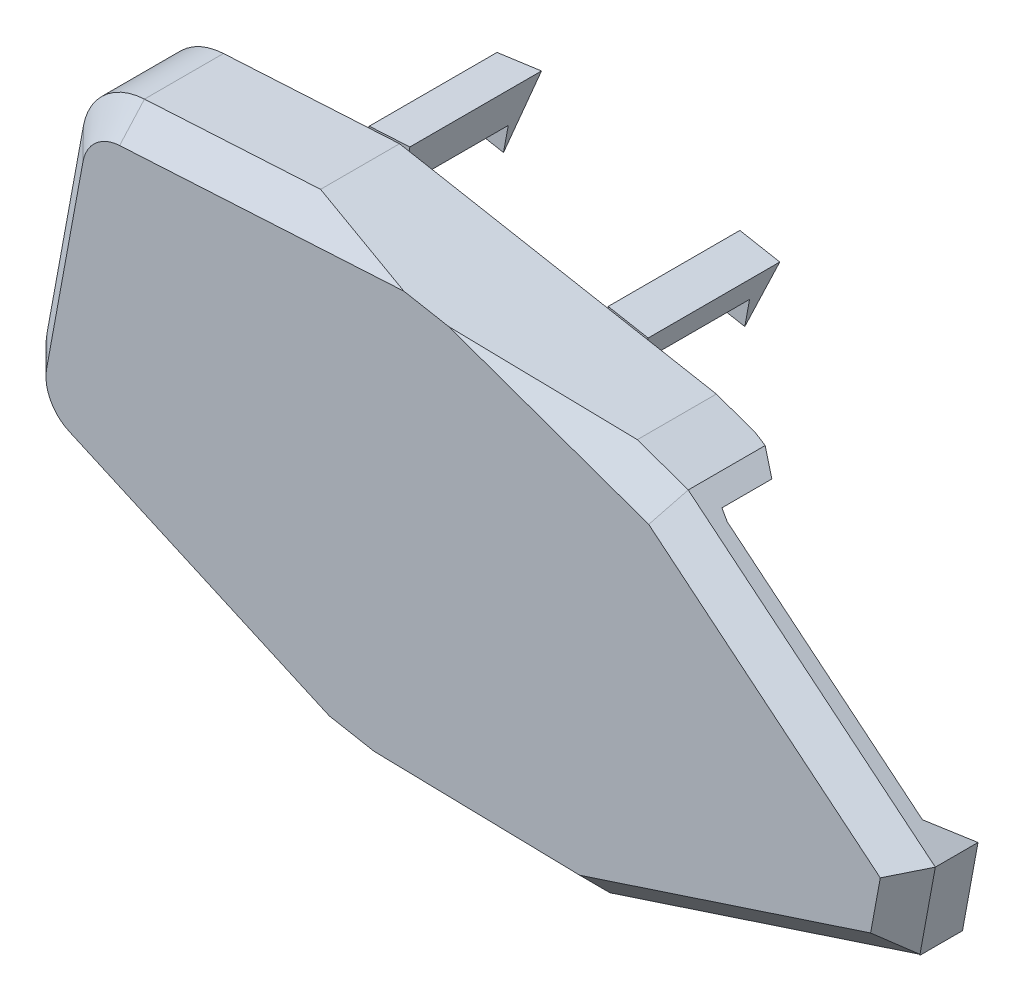
SolidWorks part; units mm, degrees
ref_plane "Front Plane" through (0, 0, 0) normal (0, 0, 1) x (1, 0, 0)
ref_plane "Top Plane" through (0, 0, 0) normal (0, 1, 0) x (1, 0, 0)
ref_plane "Right Plane" through (0, 0, 0) normal (1, 0, 0) x (0, 0, -1)
sketch "Sketch1" plane through (0, 0, 0) normal (0, 0, 1) x (1, 0, 0)
  line L0 (-54.3202, -28.2496) -> (-51.5581, -13.2557)
  line L2 (-46.9215, -9.1694) -> (-33.5467, -8.4176)
  line L3 (-33.5467, -8.4176) -> (-9.4849, -12.8501)
  line L5 (-9.4849, -12.8501) -> (10.6469, -20.0271)
  line L6 (13.8852, -25.6426) -> (11.2412, -39.9955)
  line L7 (-52.9392, -20.7527) -> (12.5632, -32.8191) construction
  line L8 (-15.1533, -43.6208) -> (6.2145, -44.0885)
  line L9 (-39.2151, -39.1883) -> (-15.1533, -43.6208)
  line L10 (-51.444, -33.7198) -> (-39.2151, -39.1883)
  arc A0 (6.2145, -44.0885) -> (11.2412, -39.9955) centre (6.3239, -39.0897) ccw
  arc A1 (10.6469, -20.0271) -> (13.8852, -25.6426) centre (8.9679, -24.7368) cw
  arc A2 (-51.444, -33.7198) -> (-54.3202, -28.2496) centre (-49.4029, -29.1554) cw
  arc A3 (-51.5581, -13.2557) -> (-46.9215, -9.1694) centre (-46.6409, -14.1616) cw
  point P16 (10.47, -44.1817)
  point P19 (14.6563, -21.4565)
  point P22 (-55.0323, -32.1153)
  point P25 (-50.846, -9.3901)
  dimension "D1" = 5
extrude "Boss-Extrude1" add sketch "Sketch1" along normal blind 8
sketch "Sketch2" plane through (0, 0, 0) normal (0, 0, -1) x (-1, 0, 0)
  line L0 (53.0576, -29.6753) -> (49.8455, -12.2387)
  line L1 (7.688, -29.0189) -> (66.6951, -18.149) construction
  line L2 (47.8786, -10.6011) -> (29.9733, -10.6011)
  line L3 (29.9733, -10.6011) -> (5.1379, -15.1761)
  line L4 (1.3472, 5.402) -> (14.0287, -63.4397) construction
  line L5 (9.4849, -12.8501) -> (33.5467, -8.4176) construction
  line L6 (33.5467, -8.4176) -> (46.9215, -9.1694) construction
  line L7 (51.5581, -13.2557) -> (54.3202, -28.2496) construction
  line L8 (5.1379, -15.1761) -> (-10.1011, -22.0315)
  line L9 (-8.9937, -21.8275) -> (-15.2261, -22.9756) construction
  line L10 (-10.1011, -22.0315) -> (-10.675, -22.2897)
  line L11 (51.4516, -20.957) -> (7.688, -29.0189) construction
  line L12 (51.8034, -31.9064) -> (35.0734, -38.2866)
  line L13 (35.0734, -38.2866) -> (10.238, -42.8617)
  line L14 (-6.4435, -41.8865) -> (-7.0718, -41.8498)
  line L15 (10.238, -42.8617) -> (-6.4435, -41.8865)
  line L16 (-8.922, -40.2155) -> (-11.8214, -24.4759)
  arc A1 (-7.0718, -41.8498) -> (-8.922, -40.2155) centre (-6.9551, -39.8532) cw
  arc A2 (51.8034, -31.9064) -> (53.0576, -29.6753) centre (51.0907, -30.0376) ccw
  arc A3 (49.8455, -12.2387) -> (47.8786, -10.6011) centre (47.8786, -12.6011) ccw
  arc A4 (-10.675, -22.2897) -> (-11.8214, -24.4759) centre (-9.8545, -24.1136) ccw
  point P26 (-8.6378, -41.7582)
  point P29 (53.3593, -31.313)
  point P32 (49.5439, -10.6011)
  point P35 (-12.1056, -22.9332)
  dimension "D4" = 2
  dimension "D1" = 1.5
  dimension "D2" = 2.3806
  dimension "D3" = 1.5
extrude "Cut-Extrude1" cut sketch "Sketch2" against normal blind 5
chamfer "Chamfer1" distance 2 angle 45 5 edges at (-4.4694, -43.8546, 8) (9.4809, -42.967, 8) (12.5632, -32.8191, 8) (13.2993, -22.239, 8) (0.581, -16.4386, 8)
chamfer "Chamfer2" distance 2 angle 45 5 edges at (-45.3295, -36.4541, 8) (-53.8285, -31.4823, 8) (-52.9392, -20.7527, 8) (-49.9468, -10.4104, 8) (-40.2341, -8.7935, 8)
sketch "Sketch3" plane through (0, 0, 0) normal (0, 0, -1) x (-1, 0, 0)
  line L0 (23.3947, -42.1026) -> (23.0981, -40.4927)
  line L1 (39.2151, -39.1883) -> (15.1533, -43.6208) construction
  line L2 (10.238, -42.8617) -> (35.0734, -38.2866) construction
  line L3 (38.0004, -36.6537) -> (38.5242, -39.4972)
  line L5 (23.3947, -42.1026) -> (20.3598, -42.6617)
  line L6 (20.3598, -42.6617) -> (20.0632, -41.0517)
  line L7 (20.0632, -41.0517) -> (23.0981, -40.4927)
  line L8 (51.444, -33.7198) -> (39.2151, -39.1883) construction
  line L9 (38.0004, -36.6537) -> (40.9507, -36.1102)
  line L10 (40.9507, -36.1102) -> (41.3425, -38.2369)
  line L11 (40.9507, -36.1102) -> (41.3131, -38.0771) construction
  line L12 (38.3627, -38.6206) -> (38.0004, -36.6537) construction
  line L13 (38.5242, -39.4972) -> (41.3425, -38.2369)
  line L14 (7.688, -29.0189) -> (20.0756, -26.7369) construction
  line L15 (7.688, -29.0189) -> (66.6951, -18.149) construction
  line L16 (33.2901, -11.0839) -> (32.7662, -8.2403)
  line L17 (33.2901, -11.0839) -> (36.2404, -10.5404)
  line L18 (36.2404, -10.5404) -> (35.8486, -8.4136)
  line L19 (32.7662, -8.2403) -> (35.8486, -8.4136)
  line L20 (14.9631, -13.3662) -> (17.9981, -12.8071)
  line L21 (14.6666, -11.7562) -> (14.9631, -13.3662)
  line L22 (17.7015, -11.1971) -> (14.6666, -11.7562)
  line L23 (17.7015, -11.1971) -> (17.9981, -12.8071)
extrude "Boss-Extrude2" add sketch "Sketch3" along normal blind 10
chamfer "Chamfer3" distance 5 angle 45 5 edges at (-1.5831, -42.3557, 0) (8.2791, -41.3521, 0) (10.3717, -32.3457, 0) (11.6258, -23.1848, 0) (2.7686, -18.7329, 0)
chamfer "Chamfer5" distance 1 angle 45 9 edges at (-29.0858, -39.3896, 0) (-40.786, -36.1405, 0) (-36.0757, -10.5707, 0) (-7.7976, -14.6861, 0) (-23.9857, -11.7041, 0) (-12.4809, -42.4485, 0) (-52.8341, -31.0177, 0) (-51.4516, -20.957, 0) (-49.1583, -11.0641, 0)
sketch "Sketch4" plane through (-7.7777, -42.2211, 0) normal (0.1812, 0.9835, 0) x (0.9835, -0.1812, 0)
  line L0 (-33.7312, 10) -> (-30.7312, 10)
  line L1 (-30.7312, 10) -> (-30.7312, 8)
  line L2 (-30.7312, 10) -> (-30.7312, 0) construction
  line L3 (-30.7312, 8) -> (-33.7312, 8)
  line L4 (-33.7312, 10) -> (-33.7312, -0.9393) construction
  line L5 (-33.7312, 8) -> (-33.7312, 10)
  dimension "D1" = 2
extrude "Boss-Extrude3" add sketch "Sketch4" along normal blind 2
sketch "Sketch5" plane through (-33.173, 6.1109, 0) normal (-0.9835, 0.1812, 0) x (0, 0, 1)
  line L0 (-8, -40.9315) -> (-10, -45.0941)
  line L1 (-10, -45.0941) -> (-10, -40.9315)
  line L2 (-10, -40.9315) -> (-8, -40.9315)
extrude "Cut-Extrude2" cut sketch "Sketch5" against normal up to next
sketch "Sketch8" plane through (-3.0674, -16.6513, 0) normal (-0.1812, -0.9835, 0) x (0.9835, -0.1812, 0)
  line L0 (-33.7312, -10) -> (-30.7312, -10)
  line L1 (-30.7312, -10) -> (-30.7312, -8)
  line L2 (-30.7312, -10) -> (-30.7312, 0) construction
  line L3 (-30.7312, -8) -> (-33.7312, -8)
  line L4 (-33.7312, -10) -> (-33.7312, 0.9393) construction
  line L5 (-33.7312, -8) -> (-33.7312, -10)
  dimension "D1" = 2
extrude "Boss-Extrude6" add sketch "Sketch8" along normal blind 2
sketch "Sketch10" plane through (-2.8725, -15.5934, 0) normal (-0.1812, -0.9835, 0) x (0.9835, -0.1812, 0)
  line L0 (-15.3801, -10) -> (-12.294, -10)
  line L1 (-12.294, -10) -> (-12.294, -8)
  line L2 (-12.294, -10) -> (-12.294, 1) construction
  line L3 (-12.294, -8) -> (-15.3801, -8)
  line L4 (-15.3801, -10) -> (-15.3801, 1) construction
  line L5 (-15.3801, -8) -> (-15.3801, -10)
  dimension "D1" = 2
extrude "Boss-Extrude7" add sketch "Sketch10" along normal blind 2
sketch "Sketch12" plane through (-12.0906, 2.2273, 0) normal (0.9835, -0.1812, 0) x (0, 0, -1)
  line L0 (8, -17.8558) -> (10, -14.2187)
  line L1 (10, -14.2187) -> (10, -17.8558)
  line L2 (10, -17.8558) -> (8, -17.8558)
extrude "Cut-Extrude6" cut sketch "Sketch12" against normal up to next
sketch "Sketch13" plane through (-30.2227, 5.5674, 0) normal (0.9835, -0.1812, 0) x (0, 0, -1)
  line L0 (8, -18.9315) -> (10, -14.0401)
  line L1 (10, -14.0401) -> (10, -18.9315)
  line L2 (10, -18.9315) -> (8, -18.9315)
extrude "Cut-Extrude7" cut sketch "Sketch13" against normal up to next
sketch "Sketch14" plane through (-7.9726, -43.279, 0) normal (0.1812, 0.9835, 0) x (0.9835, -0.1812, 0)
  line L0 (-15.3801, 10) -> (-12.294, 10)
  line L1 (-12.294, 10) -> (-12.294, 8)
  line L2 (-12.294, 10) -> (-12.294, -1) construction
  line L3 (-12.294, 8) -> (-15.3801, 8)
  line L4 (-15.3801, 10) -> (-15.3801, -1) construction
  line L5 (-15.3801, 8) -> (-15.3801, 10)
  dimension "D1" = 2
extrude "Boss-Extrude8" add sketch "Sketch14" along normal blind 2
sketch "Sketch15" plane through (-12.0906, 2.2273, 0) normal (0.9835, -0.1812, 0) x (0, 0, -1)
  line L0 (8, -42.0072) -> (10, -45.6442)
  line L1 (10, -45.6442) -> (10, -42.0072)
  line L2 (10, -42.0072) -> (8, -42.0072)
extrude "Cut-Extrude8" cut sketch "Sketch15" against normal up to next
sketch "Sketch17" plane through (0, 0, 8) normal (0, 0, 1) x (1, 0, 0)
  line L4 (13.8852, -25.6426) -> (11.2412, -39.9955) construction
  line L5 (-7.688, -29.0189) -> (12.5632, -32.8191) construction
  line L18 (13.1463, -29.6533) -> (-7.688, -12.5286)
  line L19 (-7.688, -12.5286) -> (18.2117, -20.5971)
  line L20 (18.2117, -20.5971) -> (13.1463, -29.6533)
  line L21 (-13.6664, -44.3873) -> (13.3964, -46.2574)
  line L22 (11.9589, -35.9809) -> (-13.6664, -44.3873)
  line L23 (13.3964, -46.2574) -> (11.9589, -35.9809)
extrude "Cut-Extrude9" cut sketch "Sketch17" against normal blind 10
chamfer "Chamfer6" distance 2 angle 45 2 edges at (5.1605, -23.0894, 8) (1.9827, -39.2536, 8)
